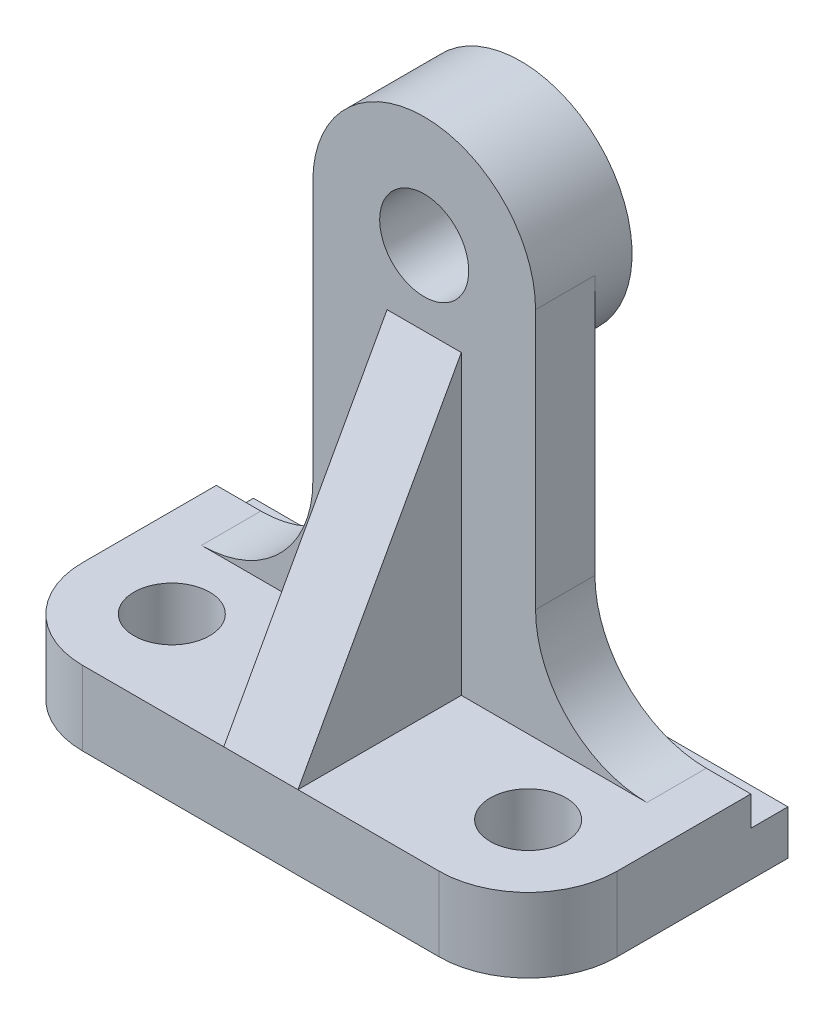
SolidWorks part; units mm, degrees
ref_plane "Front Plane" through (0, 0, 0) normal (0, 0, 1) x (1, 0, 0)
ref_plane "Top Plane" through (0, 0, 0) normal (0, 1, 0) x (1, 0, 0)
ref_plane "Right Plane" through (0, 0, 0) normal (1, 0, 0) x (0, 0, -1)
sketch "Sketch1" plane through (0, 0, 0) normal (0, 1, 0) x (1, 0, 0)
  line L1 (-24, -17.5) -> (24, -17.5)
  line L2 (-36, -5.5) -> (-36, 17.5)
  line L3 (-36, 17.5) -> (36, 17.5)
  line L4 (36, -5.5) -> (36, 17.5)
  line L5 (-36, -17.5) -> (36, 17.5) construction
  line L6 (-36, 17.5) -> (36, -17.5) construction
  arc A0 (24, -17.5) -> (36, -5.5) centre (24, -5.5) ccw
  arc A1 (-24, -17.5) -> (-36, -5.5) centre (-24, -5.5) cw
  point P0 (0, 0)
  dimension "D3" = 12
  dimension "D1" = 72
  dimension "D2" = 35
extrude "Boss-Extrude1" add sketch "Sketch1" along normal blind 10
sketch "Sketch2" plane through (-36, 0, 0) normal (-1, 0, 0) x (0, 0, 1)
  line L1 (-17.5, 10) -> (-12.5, 10)
  line L2 (-17.5, 10) -> (-17.5, 6)
  line L3 (-17.5, 6) -> (-12.5, 6)
  line L4 (-12.5, 10) -> (-12.5, 6)
  dimension "D1" = 4
  dimension "D2" = 5
extrude "Cut-Extrude1" cut sketch "Sketch2" against normal through all
sketch "Sketch3" plane through (0, 0, -12.5) normal (0, 0, -1) x (-1, 0, 0)
  line L0 (-36, 10) -> (36, 10) construction
  line L1 (-15, 60) -> (-15, 25)
  line L2 (0, 60) -> (0, 26.535) construction
  line L3 (15, 60) -> (15, 25)
  line L4 (-30, 10) -> (-30, 9)
  line L5 (-30, 9) -> (30, 9)
  line L6 (30, 9) -> (30, 10)
  circle A0 centre (0, 60) radius 6
  circle A1 centre (0, 60) radius 15
  arc A2 (-15, 25) -> (-30, 10) centre (-30, 25) cw
  arc A3 (15, 25) -> (30, 10) centre (30, 25) ccw
  dimension "D1" = 30
  dimension "D2" = 12
  dimension "D3" = 50
  dimension "D4" = 15
  dimension "D5" = 1
extrude "Boss-Extrude3" add sketch "Sketch3" against normal blind 8 contours A3 L3 A1 L1 A2 | A0 A1 region at (0, 27.1678, -12.5) region at (0, 74.5757, -12.5)
extrude "Boss-Extrude4" add sketch "Sketch3<3>" along normal blind 5 contours A0 A1 region at (0, 74.5757, -12.5)
sketch "Sketch3<3>" plane through (0, 0, -12.5) normal (0, 0, -1) x (-1, 0, 0) same geometry as "Sketch3"
sketch "Sketch4" plane through (0, 0, 0) normal (1, 0, 0) x (0, 0, -1)
  line L0 (-17.5, 10) -> (4.5, 50)
  line L1 (4.5, 60) -> (4.5, 25) construction
  line L2 (-5.5, 10) -> (12.5, 10) construction
  dimension "D1" = 40
rib "Rib1" sketch "Sketch4" sketch "Sketch4" thickness 10 extrusion direction parallel to sketch draft on no parameters "D1"=10
hole_wizard "M12 Tapped Hole1" positions "Sketch5" profile "Sketch6" tap size "M12" standard "ISO"
sketch "Sketch5" plane through (0, 10, 0) normal (0, 1, 0) x (1, 0, 0)
  arc A0 (-36, -5.5) -> (-24, -17.5) centre (-24, -5.5) ccw construction
  arc A1 (24, -17.5) -> (36, -5.5) centre (24, -5.5) ccw construction
  point P0 (-24, -5.5)
  point P2 (24, -5.5)
  point P7 (0, 0)
sketch "Sketch6" plane through (-24, 10, 5.5) normal (1, 0, 0) x (0, 0, 1)
  line L0 (0, 0) -> (0, 29.25)
  line L1 (0, 29.25) -> (5.1, 29.25)
  line L2 (5.1, 29.25) -> (5.1, 0)
  line L5 (5.1, 0) -> (0, 0)
  line L10 (0, 29.25) -> (-5.1, 29.25) construction
  line L11 (0, -6.35) -> (0, 107.95) construction
  dimension "Tap Drill Dia." = 10.2
  dimension "Tap Drill Depth" = 29.25
  dimension "Drill Angle" = 180
cosmetic thread "Hole Thread1" parameters "D1"=24, "D2"=12
cosmetic thread "Hole Thread2" parameters "D1"=24, "D2"=12
